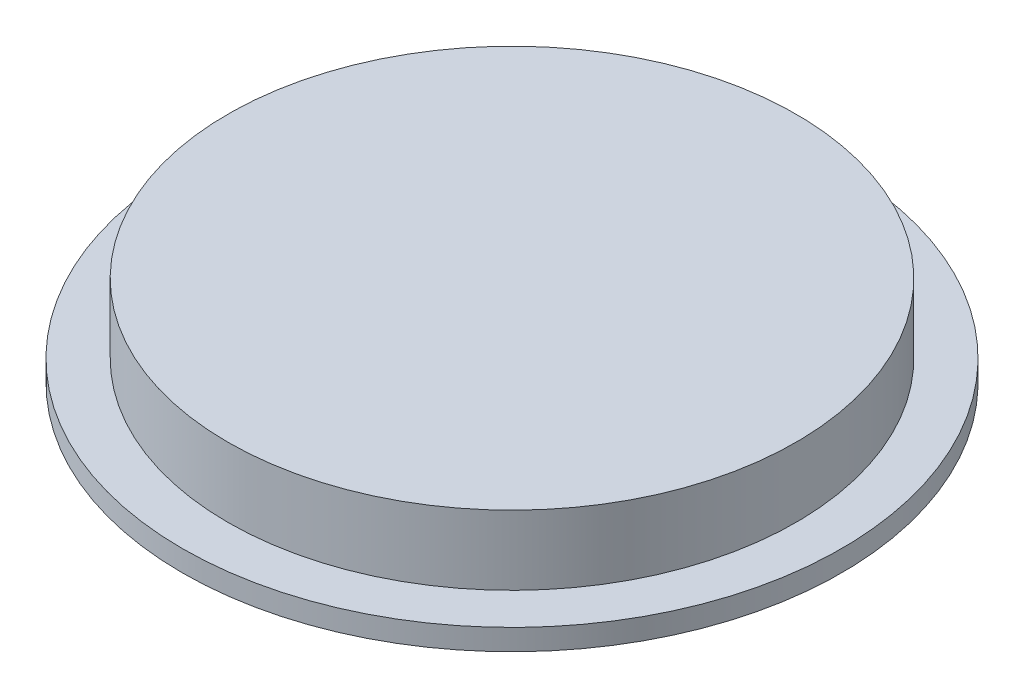
SolidWorks part; units mm, degrees
other "Camera1"
ref_plane "Front Plane" through (0, 0, 0) normal (0, 0, 1) x (1, 0, 0)
ref_plane "Top Plane" through (0, 0, 0) normal (0, 1, 0) x (1, 0, 0)
ref_plane "Right Plane" through (0, 0, 0) normal (1, 0, 0) x (0, 0, -1)
sketch "Sketch1" plane through (0, 0, 0) normal (0, 0, 1) x (1, 0, 0)
  line L0 (0, 45.2932) -> (0, -50.5102) construction
  line L1 (0, 13.5169) -> (51.9716, 13.5169)
  line L4 (60.279, -3.0367) -> (60.279, 0.8169)
  line L5 (60.279, 0.8169) -> (51.9716, 0.8169)
  line L6 (51.9716, 0.8169) -> (51.9716, 13.5169)
  line L7 (60.279, -3.0367) -> (47.1598, -3.0367)
  line L8 (47.1598, -3.0367) -> (38.1, 1.6707)
  line L9 (38.1, 1.6707) -> (0, 1.6707)
  line L10 (0, 13.5169) -> (0, 1.6707)
  point P3 (44.4178, 3.8681)
  point P7 (0, 0)
  point P13 (51.389, -3.0367)
  dimension "D1" = 38.1
  dimension "D2" = 12.7
revolve "Revolve1" add sketch "Sketch1" angle 360 about L0
